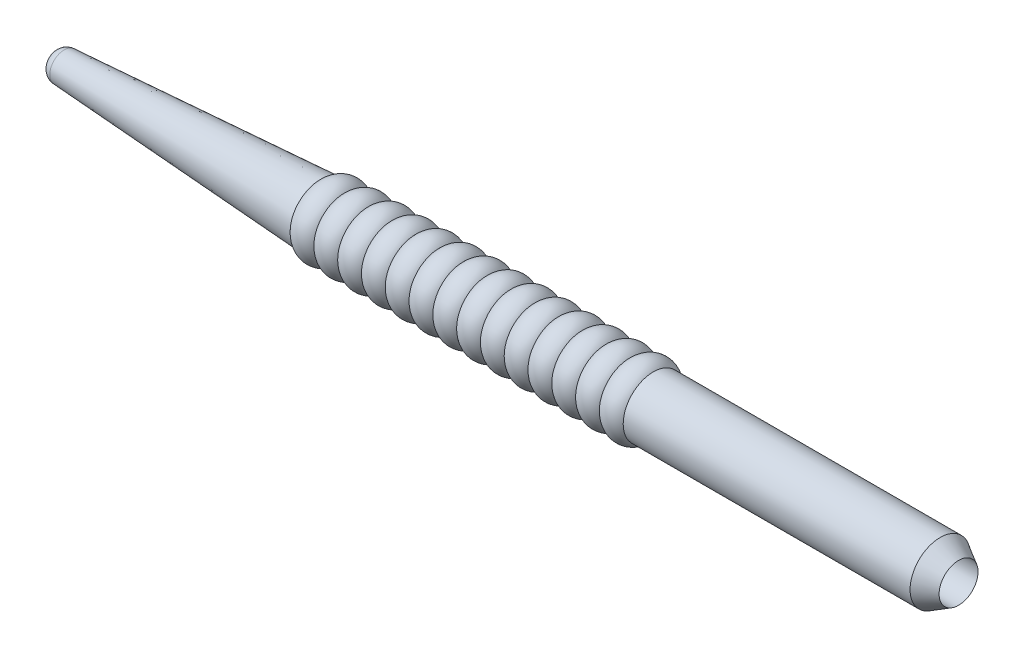
SolidWorks part; units mm, degrees
ref_plane "Front Plane" through (0, 0, 0) normal (0, 0, 1) x (1, 0, 0)
ref_plane "Top Plane" through (0, 0, 0) normal (0, 1, 0) x (1, 0, 0)
ref_plane "Right Plane" through (0, 0, 0) normal (1, 0, 0) x (0, 0, -1)
sketch "Sketch2" plane through (0, 0, 0) normal (0, 0, 1) x (1, 0, 0)
  line L0 (-19.2758, 0) -> (50, 0) construction
  line L1 (0, 21.4747) -> (0, -15.9358) construction
  line L2 (0, 0.6) -> (54.964, 3.9617) construction
  line L3 (0, 2.6) -> (55.9348, 6.0211) construction
  line L4 (0, 0.6) -> (50, 3.6581)
  line L5 (1.8707, 2.7144) -> (50, 5.6581)
  line L6 (50, 0) -> (50, 20.2328) construction
  line L7 (50, 5.6581) -> (50, 3.6581)
  arc A0 (0, 0.6) -> (1.8707, 2.7144) centre (1.9925, 0.7219) cw
  dimension "D1" = 3.5
  dimension "D2" = 0.6
  dimension "D3" = 2
  dimension "D4" = 50
revolve "Revolve2" add sketch "Sketch2" angle 360 about L0
ref_plane "Plane1" through (50, 0, 0) normal (1, 0, 0) x (0, 0, -1)
ref_axis "Axis1" through (50, 0, 0) along (-1, 0, 0)
sketch "Sketch4" plane through (0, 0, 0) normal (0, 0, 1) x (1, 0, 0)
  line L0 (21.0248, 0) -> (136.6735, 0) construction
  line L1 (50, 0) -> (0, 0) construction
  line L2 (50, 5.6581) -> (1.8707, 2.7144) construction
  line L3 (50, -6.2239) -> (50, 6.2239) construction
  line L4 (112.6099, 5.6581) -> (136.6735, 5.6581) construction
  line L5 (112.6099, 3.6581) -> (136.6735, 3.6581) construction
  line L7 (112.6099, 5.6581) -> (120, 5.6581)
  line L8 (50, 5.6581) -> (50, 3.6581)
  line L9 (112.6099, 3.6581) -> (120, 3.6581)
  line L10 (120, 5.6581) -> (120, 3.6581)
  arc A0 (50, 3.6581) -> (54.4721, 3.6581) centre (52.2361, 5.6581) ccw
  arc A1 (54.4721, 3.6581) -> (58.9443, 3.6581) centre (56.7082, 5.6581) ccw
  arc A2 (58.9443, 3.6581) -> (63.4164, 3.6581) centre (61.1803, 5.6581) ccw
  arc A3 (63.4164, 3.6581) -> (67.8885, 3.6581) centre (65.6525, 5.6581) ccw
  arc A4 (67.8885, 3.6581) -> (72.3607, 3.6581) centre (70.1246, 5.6581) ccw
  arc A5 (72.3607, 3.6581) -> (76.8328, 3.6581) centre (74.5967, 5.6581) ccw
  arc A6 (76.8328, 3.6581) -> (81.305, 3.6581) centre (79.0689, 5.6581) ccw
  arc A7 (81.305, 3.6581) -> (85.7771, 3.6581) centre (83.541, 5.6581) ccw
  arc A8 (85.7771, 3.6581) -> (90.2492, 3.6581) centre (88.0132, 5.6581) ccw
  arc A9 (90.2492, 3.6581) -> (94.7214, 3.6581) centre (92.4853, 5.6581) ccw
  arc A10 (94.7214, 3.6581) -> (99.1935, 3.6581) centre (96.9574, 5.6581) ccw
  arc A11 (99.1935, 3.6581) -> (103.6656, 3.6581) centre (101.4296, 5.6581) ccw
  arc A12 (103.6656, 3.6581) -> (108.1378, 3.6581) centre (105.9017, 5.6581) ccw
  arc A13 (108.1378, 3.6581) -> (112.6099, 3.6581) centre (110.3738, 5.6581) ccw
  arc A14 (50, 5.6581) -> (54.4721, 5.6581) centre (52.2361, 3.6581) cw
  arc A15 (54.4721, 5.6581) -> (58.9443, 5.6581) centre (56.7082, 3.6581) cw
  arc A16 (58.9443, 5.6581) -> (63.4164, 5.6581) centre (61.1803, 3.6581) cw
  arc A17 (63.4164, 5.6581) -> (67.8885, 5.6581) centre (65.6525, 3.6581) cw
  arc A18 (67.8885, 5.6581) -> (72.3607, 5.6581) centre (70.1246, 3.6581) cw
  arc A19 (72.3607, 5.6581) -> (76.8328, 5.6581) centre (74.5967, 3.6581) cw
  arc A20 (76.8328, 5.6581) -> (81.305, 5.6581) centre (79.0689, 3.6581) cw
  arc A21 (81.305, 5.6581) -> (85.7771, 5.6581) centre (83.541, 3.6581) cw
  arc A22 (85.7771, 5.6581) -> (90.2492, 5.6581) centre (88.0132, 3.6581) cw
  arc A23 (90.2492, 5.6581) -> (94.7214, 5.6581) centre (92.4853, 3.6581) cw
  arc A24 (94.7214, 5.6581) -> (99.1935, 5.6581) centre (96.9574, 3.6581) cw
  arc A25 (99.1935, 5.6581) -> (103.6656, 5.6581) centre (101.4296, 3.6581) cw
  arc A26 (103.6656, 5.6581) -> (108.1378, 5.6581) centre (105.9017, 3.6581) cw
  arc A27 (108.1378, 5.6581) -> (112.6099, 5.6581) centre (110.3738, 3.6581) cw
  point P5 (50, 5.6581)
  point P29 (0, 0)
  point P88 (0, 0)
  dimension "D3" = 3
  dimension "D5" = 3
  dimension "D1" = 2
  dimension "D2" = 70
  dimension "D4" = 14
  dimension "D6" = 14
revolve "Revolve3" add sketch "Sketch4" angle 360 about L0
ref_plane "Plane2" through (120, 0, 0) normal (1, 0, 0) x (0, 0, -1)
sketch "Sketch5" plane through (0, 0, 0) normal (0, 0, 1) x (1, 0, 0)
  line L0 (115.9016, 0) -> (205.5041, 0) construction
  line L1 (120, 5.6581) -> (205.5041, 5.6581) construction
  line L2 (120, -6.2239) -> (120, 6.2239) construction
  line L3 (120, 5.6581) -> (112.6099, 5.6581) construction
  line L4 (120, 3.6581) -> (210.3776, 3.6581) construction
  line L5 (120, 3.6581) -> (120, 5.6581)
  line L6 (120, 5.6581) -> (166.5359, 5.6581)
  line L7 (120, 3.6581) -> (170, 3.6581)
  line L8 (166.5359, 5.6581) -> (170, 3.6581)
  dimension "D1" = 2
  dimension "D2" = 30
  dimension "D3" = 50
revolve "Revolve4" add sketch "Sketch5" angle 360 about L0
